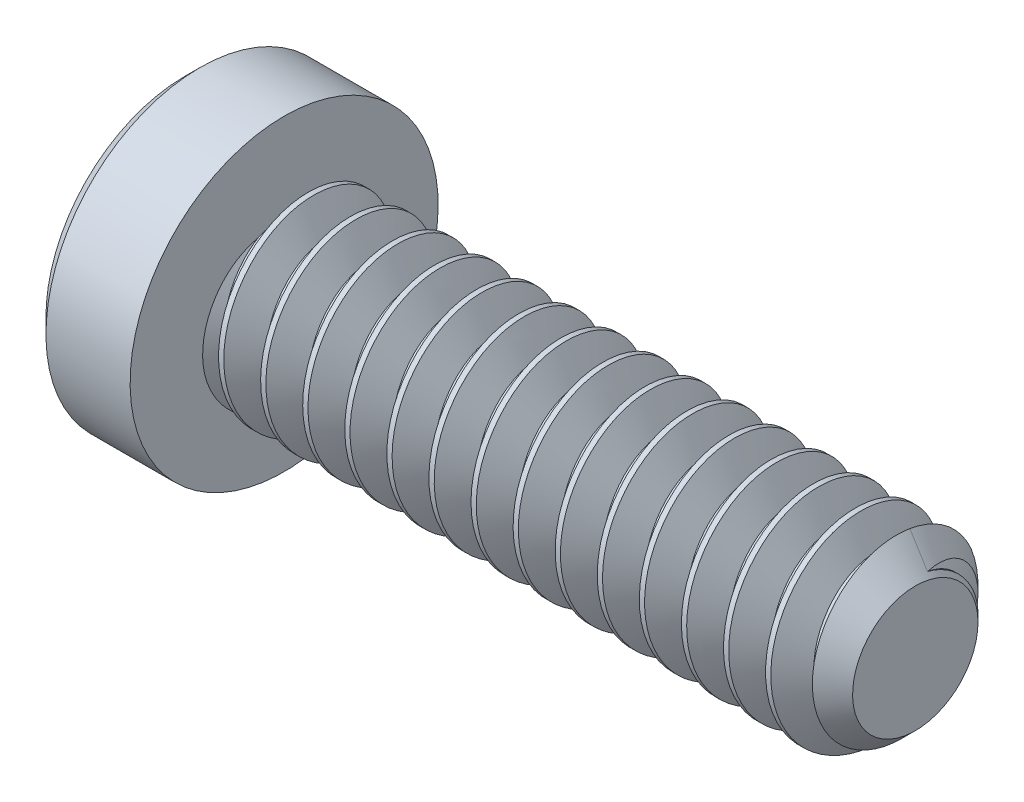
SolidWorks part; units mm, degrees
ref_plane "Front Plane" through (0, 0, 0) normal (0, 0, 1) x (1, 0, 0)
ref_plane "Top Plane" through (0, 0, 0) normal (0, 1, 0) x (1, 0, 0)
ref_plane "Right Plane" through (0, 0, 0) normal (1, 0, 0) x (0, 0, -1)
sketch "Sketch1" plane through (0, 0, 0) normal (0, 0, 1) x (1, 0, 0)
  line L0 (4.7625, 0) -> (-4.7625, 0) construction
  line L1 (4.7625, 1.4224) -> (4.7625, -1.4224) construction
  line L2 (-4.7625, 2.3241) -> (-4.7625, -2.3241) construction
  line L3 (-4.7625, 2.3241) -> (-6.0325, 2.3241) construction
  line L4 (-6.0325, 2.3241) -> (-6.2611, 2.0955) construction
  line L5 (-6.2611, 2.0955) -> (-6.2611, -2.0955) construction
  line L6 (-6.2611, -2.0955) -> (-6.0325, -2.3241) construction
  line L7 (-6.0325, -2.3241) -> (-4.7625, -2.3241) construction
  point P7 (-5.2959, 0)
  point P12 (2.2225, -1.4224)
  dimension "D1" = 45
  dimension "Dec." = 2.8448
  dimension "Length" = 9.525
  dimension "Head Dia" = 4.6482
  dimension "Head Height" = 1.4986
  dimension "Hex Depth" = 0.9652
  dimension "Chamfer" = 0.2286
  dimension "D2" = 2.54
ref_plane "Plane1" through (4.7625, 0, 0) normal (1, 0, 0) x (0, 0, -1)
ref_plane "Plane2" through (-6.2611, 0, 0) normal (1, 0, 0) x (0, 0, -1)
sketch "Sketch2" plane through (4.7625, 0, 0) normal (1, 0, 0) x (0, 0, -1)
  circle A0 centre (0, 0) radius 1.4224
extrude "Boss-Extrude1" add sketch "Sketch2" against normal up to vertex (9.525 mm away) up to point (-4.7625, 0, 0)
sketch "Sketch3" plane through (4.7625, 0, 0) normal (1, 0, 0) x (0, 0, -1)
  circle A0 centre (0, 0) radius 1.4224 construction
  circle A1 centre (0, 0) radius 1.4224
curve "Helix/Spiral1" pitch 0.635 height 10.16 radius 1.4224 centre (4.7625, 0, 0) axis (-1, 0, 0) start towards (0, 1, 0) parameters "Pitch"=0.635
chamfer "Chamfer1" distance 0.4763 angle 45 1 edges at (4.7625, 0, -1.4224)
sketch "Sketch5" plane through (0, 0, 0) normal (0, 0, 1) x (1, 0, 0)
  line L0 (4.4847, 1.4224) -> (5.0403, 1.4224)
  line L1 (5.0403, 1.4224) -> (4.8022, 1.01)
  line L2 (4.8022, 1.01) -> (4.7228, 1.01)
  line L3 (4.7228, 1.01) -> (4.4847, 1.4224)
  line L4 (4.7625, 1.01) -> (4.7625, 1.4224) construction
  line L5 (4.6037, 1.2162) -> (4.9212, 1.2162) construction
  dimension "D1" = 60
  dimension "D2" = 0.3175
  dimension "D3" = 0.0794
sweep "Cut-Sweep1" cut profiles "Sketch5" path "Helix/Spiral1" align with end faces yes
sketch "Sketch4" plane through (-6.2611, 0, 0) normal (1, 0, 0) x (0, 0, -1)
  line L0 (-2.3241, 0.7937) -> (2.3241, 0.7937) construction
  line L1 (0, 0.7332) -> (-0.635, 0.3666)
  line L2 (-0.635, 0.3666) -> (-0.635, -0.3666)
  line L3 (-0.635, -0.3666) -> (0, -0.7332)
  line L4 (0, -0.7332) -> (0.635, -0.3666)
  line L5 (0.635, -0.3666) -> (0.635, 0.3666)
  line L6 (0.635, 0.3666) -> (0, 0.7332)
  line L7 (0, 0) -> (0, 0.7937) construction
  circle A0 centre (0, 0) radius 0.635 construction
  dimension "Hex Size" = 1.27
  dimension "D1" = 4.6482
  dimension "D2" = 0.7937
sketch "Sketch6" plane through (0, 0, 0) normal (0, 0, 1) x (1, 0, 0)
  line L0 (-6.0325, 2.3241) -> (-6.2611, 2.0955) construction
  line L1 (-4.7625, 2.3241) -> (-6.0325, 2.3241) construction
  line L2 (-4.7625, 2.3241) -> (-4.7625, -2.3241) construction
  line L3 (-6.2611, 2.0955) -> (-6.2611, -2.0955) construction
  line L4 (-6.0325, 2.3241) -> (-6.2611, 2.0955)
  line L5 (-4.7625, 2.3241) -> (-6.0325, 2.3241)
  line L6 (-4.7625, 2.3241) -> (-4.7625, 0)
  line L7 (-6.2611, 2.0955) -> (-6.2611, 0)
  line L8 (-4.7625, 0) -> (-6.2611, 0) construction
  line L9 (-4.7625, 0) -> (-6.2611, 0)
revolve "Revolve1" add sketch "Sketch6" angle 360 about L8
extrude "Cut-Extrude1" cut sketch "Sketch4" along normal up to vertex (0.9652 mm away) up to point (-5.2959, 0, 0)
sketch "Sketch8" plane through (-6.2611, 0, 0) normal (-1, 0, 0) x (0, 0, 1)
  circle A1 centre (0, 0) radius 0.7332
extrude "Cut-Extrude2" cut sketch "Sketch8" against normal through all draft 45
equation "\"D3@Helix/Spiral1\" = \"Length@Sketch1\"+\"Pitch@Helix/Spiral1\""
equation "\"D3@Sketch5\" = \"Pitch@Helix/Spiral1\"*.125"
equation "\"D2@Sketch5\" = \"Pitch@Helix/Spiral1\"*.50"
equation "\"D1@Chamfer1\" = \"Pitch@Helix/Spiral1\"*.75"
equation "\"D2@Sketch1\" = \"Pitch@Helix/Spiral1\"*4"
equation "\"D1@Sketch4\" = \"Head Dia@Sketch1\""
